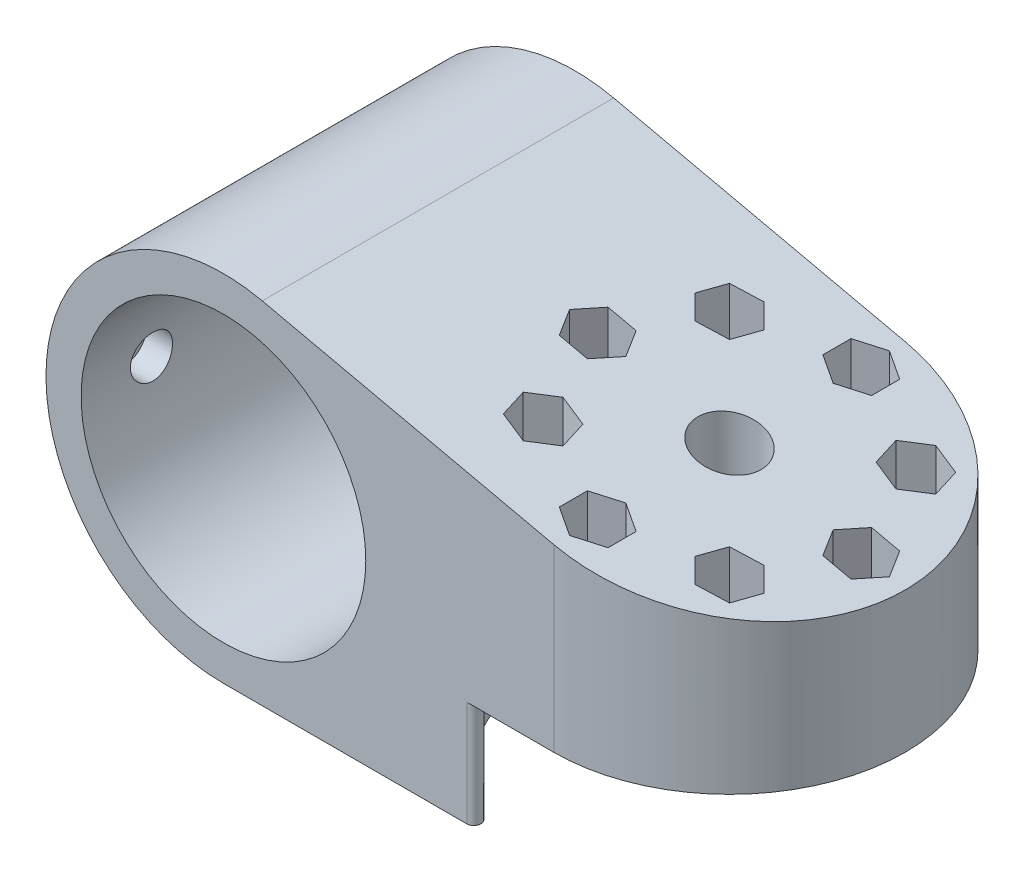
SolidWorks part; units mm, degrees
other "标注1"
sketch "草图15" plane through (25, 50, -25) normal (0.8598, 0.5009, -0.0991) x (0.178, -0.4759, -0.8613)
ref_plane "前视基准面" through (0, 0, 0) normal (0, 0, 1) x (1, 0, 0)
ref_plane "上视基准面" through (0, 0, 0) normal (0, 1, 0) x (1, 0, 0)
ref_plane "右视基准面" through (0, 0, 0) normal (1, 0, 0) x (0, 0, -1)
other "Configuration Table"
sketch "草图1" plane through (0, 0, 0) normal (0, 1, 0) x (1, 0, 0)
  line L0 (0, 25) -> (-25, 25)
  line L1 (-25, 25) -> (-25, 0)
  line L2 (-25, 0) -> (-25, -25)
  line L3 (-25, -25) -> (0, -25)
  circle A0 centre (0, 0) radius 12.5
  arc A1 (0, -25) -> (0, 25) centre (0, 0) ccw
  dimension "D1" = 25
  dimension "D2" = 50
extrude "凸台-拉伸1" add sketch "草图1" along normal blind 10
sketch "草图2" plane through (0, 10, 0) normal (0, 1, 0) x (1, 0, 0)
  line L0 (0, 25) -> (-25, 25)
  line L1 (-25, 25) -> (-25, 0)
  line L2 (-25, 0) -> (-25, -25)
  line L3 (-25, -25) -> (0, -25)
  arc A0 (0, -25) -> (0, 25) centre (0, 0) ccw
  circle A1 centre (0, 0) radius 4.5
  circle A2 centre (0, 0) radius 25 construction
  dimension "D1" = 9
extrude "凸台-拉伸2" add sketch "草图2" along normal blind 10
ref_plane "基准面1" through (0, 0, 12) normal (0, 0, 1) x (1, 0, 0)
sketch "草图13" plane through (0, 0, 0) normal (0, 0, 1) x (1, 0, 0)
  line L5 (-25, 20) -> (25, 20)
  line L6 (25, 20) -> (0, 20) construction
  line L7 (0, 0) -> (25, 0) construction
  line L8 (-25, 0) -> (-25, 20)
  line L9 (25, 20) -> (0, 20) construction
  line L10 (-25, 20) -> (-25, 0) construction
  line L11 (25, 20) -> (-41.4816, 34.8895)
  line L12 (-25, 0) -> (-25, -15)
  line L13 (-25, -15) -> (-47.06, -15)
  circle A0 centre (-47, 10.2499) radius 20.25
  arc A1 (-41.4816, 34.8895) -> (-67.8132, 24.5458) centre (-47, 10.2499) ccw
  arc A2 (-67.8132, 24.5458) -> (-47.06, -15) centre (-47, 10.2499) ccw
  point P2 (-51.5587, -14.736)
  point P13 (-36.2341, -15)
  point P14 (25, 22.0245)
  point P17 (-29.4988, -15)
  point P19 (25.5127, 20)
  dimension "D1" = 40.5
  dimension "D4" = 5
  dimension "D2" = 15
  dimension "D3" = 22
extrude "凸台-拉伸4" add sketch "草图13" along normal blind 25 and the other way blind 25
sketch "草图8" plane through (0, 0, 0) normal (0, -1, 0) x (1, 0, 0)
  line L0 (-1000, 0) -> (49000, 0) construction
  line L1 (0, -1000) -> (0, 49000) construction
  line L2 (-707.1068, -707.1068) -> (34648.2323, 34648.2323) construction
  circle A0 centre (0, 0) radius 18.75 construction
  circle A1 centre (18.75, 0) radius 2.5
  circle A2 centre (13.2583, 13.2583) radius 2.5
  circle A3 centre (0, 18.75) radius 2.5
  circle A4 centre (-18.75, 0) radius 2.5
  circle A5 centre (-13.2583, 13.2583) radius 2.5
  circle A6 centre (13.2583, -13.2583) radius 2.5
  circle A7 centre (0, -18.75) radius 2.5
  circle A8 centre (-13.2583, -13.2583) radius 2.5
  circle A9 centre (0, 0) radius 4.5
  dimension "D2" = 37.5
  dimension "D3" = 5
  dimension "D4" = 5
  dimension "D5" = 9
  dimension "D1" = 45
extrude "切除-拉伸2" cut sketch "草图8" against normal through all
ref_plane "基准面2" through (0, 18.5, 0) normal (0, 1, 0) x (1, 0, 0)
sketch "草图11" plane through (0, 18.5, 0) normal (0, 1, 0) x (1, 0, 0)
  line L0 (-1000.0592, 0) -> (48999.9408, 0) construction
  line L1 (0, -1000) -> (0, 49000) construction
  line L2 (-707.1068, -707.1068) -> (34648.2323, 34648.2323) construction
  line L3 (0, -14.75) -> (-3.4641, -16.75)
  line L4 (-3.4641, -16.75) -> (-3.4641, -20.75)
  line L5 (-3.4641, -20.75) -> (0, -22.75)
  line L6 (0, -22.75) -> (3.4641, -20.75)
  line L7 (3.4641, -20.75) -> (3.4641, -16.75)
  line L8 (3.4641, -16.75) -> (0, -14.75)
  line L9 (-382.6834, -923.8795) -> (18751.4882, 45270.0971) construction
  line L10 (0, -18.75) -> (-3.4641, -16.75) construction
  line L11 (-14.2935, -9.3945) -> (-10.4298, -10.4298)
  line L12 (-17.122, -12.223) -> (-14.2935, -9.3945)
  line L13 (-16.0867, -16.0867) -> (-17.122, -12.223)
  line L14 (-12.223, -17.122) -> (-16.0867, -16.0867)
  line L15 (-9.3945, -14.2935) -> (-12.223, -17.122)
  line L16 (-10.4298, -10.4298) -> (-9.3945, -14.2935)
  line L17 (10.4298, -10.4298) -> (9.3945, -14.2935)
  line L18 (9.3945, -14.2935) -> (12.223, -17.122)
  line L19 (12.223, -17.122) -> (16.0867, -16.0867)
  line L20 (16.0867, -16.0867) -> (17.122, -12.223)
  line L21 (17.122, -12.223) -> (14.2935, -9.3945)
  line L22 (14.2935, -9.3945) -> (10.4298, -10.4298)
  line L23 (-9.3945, 14.2935) -> (-10.4298, 10.4298)
  line L24 (-12.223, 17.122) -> (-9.3945, 14.2935)
  line L25 (-16.0867, 16.0867) -> (-12.223, 17.122)
  line L26 (-17.122, 12.223) -> (-16.0867, 16.0867)
  line L27 (-14.2935, 9.3945) -> (-17.122, 12.223)
  line L28 (-10.4298, 10.4298) -> (-14.2935, 9.3945)
  line L29 (-16.75, 3.4641) -> (-14.75, 0)
  line L30 (-20.75, 3.4641) -> (-16.75, 3.4641)
  line L31 (-22.75, 0) -> (-20.75, 3.4641)
  line L32 (-20.75, -3.4641) -> (-22.75, 0)
  line L33 (-16.75, -3.4641) -> (-20.75, -3.4641)
  line L34 (-14.75, 0) -> (-16.75, -3.4641)
  line L35 (10.4298, 10.4298) -> (14.2935, 9.3945)
  line L36 (14.2935, 9.3945) -> (17.122, 12.223)
  line L37 (17.122, 12.223) -> (16.0867, 16.0867)
  line L38 (16.0867, 16.0867) -> (12.223, 17.122)
  line L39 (12.223, 17.122) -> (9.3945, 14.2935)
  line L40 (9.3945, 14.2935) -> (10.4298, 10.4298)
  line L41 (14.75, 0) -> (16.75, -3.4641)
  line L42 (16.75, -3.4641) -> (20.75, -3.4641)
  line L43 (20.75, -3.4641) -> (22.75, 0)
  line L44 (22.75, 0) -> (20.75, 3.4641)
  line L45 (20.75, 3.4641) -> (16.75, 3.4641)
  line L46 (16.75, 3.4641) -> (14.75, 0)
  line L47 (3.4641, 16.75) -> (0, 14.75)
  line L48 (3.4641, 20.75) -> (3.4641, 16.75)
  line L49 (0, 22.75) -> (3.4641, 20.75)
  line L50 (-3.4641, 20.75) -> (0, 22.75)
  line L51 (-3.4641, 16.75) -> (-3.4641, 20.75)
  line L52 (0, 14.75) -> (-3.4641, 16.75)
  circle A9 centre (0, 0) radius 18.75 construction
  dimension "D1" = 45
  dimension "D2" = 120
  dimension "D3" = 4
  dimension "D4" = 22.5
  dimension "D5" = 60
extrude "切除-拉伸6" cut sketch "草图11" against normal offset from surface 5 and the other way through all up to face at (18.75, 0, -2.5)
sketch "草图14" plane through (0, 0, 0) normal (0, -1, 0) x (1, 0, 0)
  line L0 (0, 25) -> (25, 25) construction
  line L1 (0, -25) -> (25, -25) construction
  line L2 (0, 25) -> (25, 25)
  line L3 (25, 25) -> (25, 0)
  line L4 (0, -25) -> (25, -25)
  line L5 (25, -25) -> (25, 0)
  circle A0 centre (0, 0) radius 4.5
  arc A1 (0, 25) -> (25, 0) centre (0, 0) cw
  arc A2 (25, 0) -> (0, 25) centre (0, 0) ccw construction
  arc A3 (0, -25) -> (25, 0) centre (0, 0) ccw construction
  arc A4 (25, 0) -> (0, -25) centre (0, 0) cw
  point P16 (0, 0)
  point P21 (0, 0)
  arc M9 (0, -25) -> (0, 25) centre (0, 0) ccw
  dimension "D1" = 9
extrude "切除-拉伸8" cut sketch "草图14" against normal through all contours L3 L2 M9 | L4 L5 M9 region at (19.4158, 0, -19.4158) region at (19.4158, 0, 19.4158)
ref_plane "基准面3" through (-50, 0, 0) normal (1, 0, 0) x (0, 0, -1)
sketch "草图16" plane through (-50, 0, 0) normal (1, 0, 0) x (0, 0, -1)
  line L0 (-15, -10.0001) -> (-15, 30.4999) construction
  line L2 (15, -10.0001) -> (15, 30.4999) construction
  line L4 (-25, 35.4999) -> (-25, -15) construction
  line L5 (25, -15) -> (25, 35.4999) construction
  line L7 (-15, 30.4999) -> (15, 30.4999) construction
  line L8 (25, 30.4999) -> (-25, 30.4999) construction
  line L9 (15, -10.0001) -> (-15, -10.0001) construction
  line L10 (-25, -10.0001) -> (25, -10.0001) construction
  circle A0 centre (-15, 10.2499) radius 2
  circle A1 centre (15, 10.2499) radius 2
  dimension "D3" = 4
  dimension "D4" = 4
  dimension "D1" = 10
  dimension "D2" = 10
extrude "切除-拉伸9" cut sketch "草图16" against normal blind 43
ref_plane "基准面4" through (-67, 0, 0) normal (1, 0, 0) x (0, 0, -1)
sketch "草图17" plane through (-67, 0, 0) normal (1, 0, 0) x (0, 0, -1)
  circle A0 centre (-15, 10.2499) radius 3
  circle A1 centre (15, 10.2499) radius 3
  dimension "D1" = 6
  dimension "D2" = 6
extrude "切除-拉伸10" cut sketch "草图17" against normal blind 4
sketch "草图18" plane through (0, 0, 0) normal (0, -1, 0) x (1, 0, 0)
  circle A0 centre (0, 0) radius 26
  dimension "D1" = 52
extrude "切除-拉伸11" cut sketch "草图18" along normal up to surface (15 mm away) up to face at (-36.03, -15, 0)
sketch "草图19" plane through (0, 0, 0) normal (0, -1, 0) x (1, 0, 0)
  line L0 (-25, 25) -> (0, 25) construction
  line L1 (0, -25) -> (-25, -25) construction
  line L2 (-7.1414, 25) -> (-25, 25)
  line L3 (-25, 25) -> (-25, 7.1414)
  line L4 (-25, -7.1414) -> (-25, -25)
  line L5 (-25, -25) -> (-7.1414, -25)
  arc A0 (-25, 7.1414) -> (-7.1414, 25) centre (0, 0) cw
  arc A1 (-25, -7.1414) -> (-7.1414, -25) centre (0, 0) ccw
extrude "凸台-拉伸5" add sketch "草图19" along normal up to surface (15 mm away) up to face at (-32.52, -15, 0)
fillet "圆角1" radius 1 2 edges at (-7.1414, -7.5, -25) (-7.1414, -7.5, 25)
